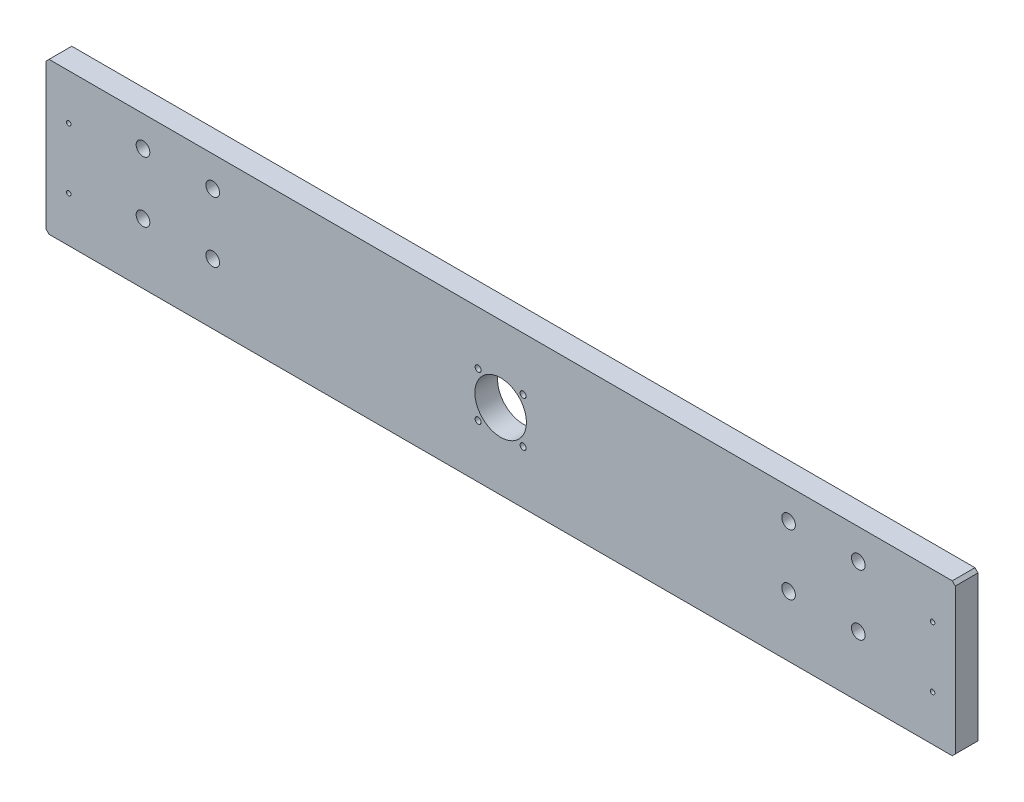
SolidWorks part; units mm, degrees
ref_plane "Piano frontale" through (0, 0, 0) normal (0, 0, 1) x (1, 0, 0)
ref_plane "Piano superiore" through (0, 0, 0) normal (0, 1, 0) x (1, 0, 0)
ref_plane "Piano destro" through (0, 0, 0) normal (1, 0, 0) x (0, 0, -1)
sketch "Schizzo1" plane through (0, 0, 0) normal (0, 0, 1) x (1, 0, 0)
  line L0 (300, 100) -> (300, 0) construction
  line L1 (2, 0) -> (598, 0)
  line L2 (0, 2) -> (0, 98)
  line L3 (2, 100) -> (598, 100)
  line L4 (600, 2) -> (600, 98)
  line L5 (300, 50) -> (274.8765, 75.1235) construction
  line L6 (64, 80) -> (536, 80) construction
  line L7 (300, 50) -> (318.5099, 50) construction
  line L8 (87, 80) -> (87, 40) construction
  line L21 (0, 98) -> (2, 100)
  line L22 (2, 0) -> (0, 2)
  line L23 (598, 0) -> (600, 2)
  line L24 (598, 100) -> (600, 98)
  line L25 (300, 50) -> (600, 50) construction
  circle A0 centre (300, 50) radius 17
  circle A1 centre (300, 50) radius 21 construction
  circle A2 centre (314.8492, 64.8492) radius 2
  circle A3 centre (110, 40) radius 4.5
  circle A4 centre (314.8492, 35.1508) radius 2
  circle A5 centre (285.1508, 35.1508) radius 2
  circle A6 centre (110, 80) radius 4.5
  circle A7 centre (536, 40) radius 4.5
  circle A8 centre (64, 40) radius 4.5
  circle A9 centre (64, 80) radius 4.5
  circle A10 centre (490, 40) radius 4.5
  circle A11 centre (15, 30) radius 1.5
  circle A12 centre (585, 30) radius 1.5
  circle A13 centre (285.1508, 64.8492) radius 2
  circle A14 centre (490, 80) radius 4.5
  circle A15 centre (536, 80) radius 4.5
  circle A17 centre (585, 70) radius 1.5
  circle A18 centre (15, 70) radius 1.5
  point P0 (0, 0)
  point P1 (600, 100)
  point P2 (0, 100)
  point P3 (600, 0)
  point P13 (285.1508, 64.8492)
  point P14 (314.8492, 64.8492)
  point P15 (285.1508, 35.1508)
  point P17 (314.8492, 35.1508)
  dimension "D4" = 34
  dimension "D10" = 64
  dimension "D15" = 3
  dimension "D17" = 4
  dimension "D8" = 42
  dimension "D1" = 100
  dimension "D2" = 600
  dimension "D3" = 50
  dimension "D5" = 45
  dimension "D6" = 20
  dimension "D7" = 40
  dimension "D9" = 23
  dimension "D14" = 30
  dimension "D16" = 15
extrude "Estrusione-Estrusione1" add sketch "Schizzo1" against normal blind 15
sketch "Sketch1" plane through (0, 0, 0) normal (0, -1, 0) x (1, 0, 0)
  line L0 (2, -7.5) -> (598, -7.5) construction
  line L1 (2, -15) -> (2, 0) construction
  line L2 (598, -15) -> (598, 0) construction
  line L3 (300, 0) -> (300, -15) construction
  line L4 (2, 0) -> (598, 0) construction
  line L5 (2, -15) -> (598, -15) construction
  line L6 (0, -15) -> (0, 0) construction
  point P12 (30, -7.5)
  point P15 (570, -7.5)
  dimension "D1" = 30
hole_wizard "M8 Tapped Hole1" positions "3DSketch2" profile "Sketch2" tap size "M8" standard "ISO"
sketch3d "3DSketch2"
  point P0 (30, 0, -7.5)
  point P3 (570, 0, -7.5)
sketch "Sketch2" plane through (30, 0, -7.5) normal (1, 0, 0) x (0, 0, -1)
  line L0 (0, 0) -> (0, 25.7929)
  line L1 (0, 25.7929) -> (3.4, 23.75)
  line L2 (3.4, 23.75) -> (3.4, 0)
  line L5 (3.4, 0) -> (0, 0)
  line L10 (0, 25.7929) -> (-3.4, 23.75) construction
  line L11 (0, -6.35) -> (0, 107.95) construction
  dimension "Tap Drill Dia." = 6.8
  dimension "Tap Drill Depth" = 23.75
  dimension "Drill Angle" = 118
